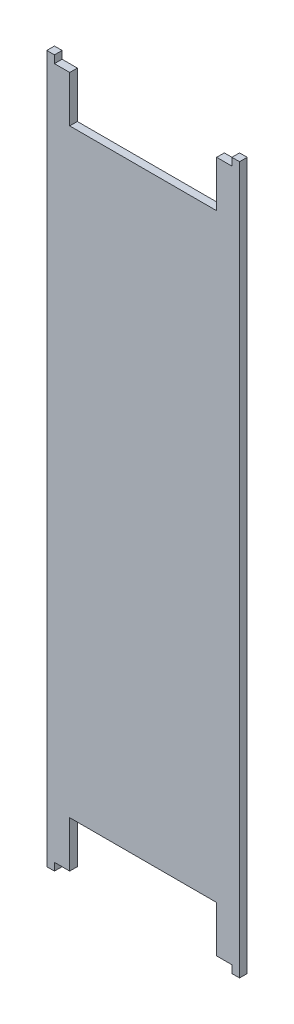
SolidWorks part; units mm, degrees
ref_plane "Front Plane" through (0, 0, 0) normal (0, 0, 1) x (1, 0, 0)
ref_plane "Top Plane" through (0, 0, 0) normal (0, 1, 0) x (1, 0, 0)
ref_plane "Right Plane" through (0, 0, 0) normal (1, 0, 0) x (0, 0, -1)
sketch "Sketch1" plane through (0, 0, 0) normal (0, 0, 1) x (1, 0, 0)
  line L0 (0.9075, 0) -> (-0.9075, 0) construction
  line L1 (-20.825, 76.375) -> (20.825, 76.375)
  line L2 (-20.825, 76.375) -> (-20.825, -76.375)
  line L3 (-20.825, -76.375) -> (20.825, -76.375)
  line L4 (20.825, 76.375) -> (20.825, -76.375)
  line L5 (0, -0.9075) -> (0, 0.9075) construction
  point P6 (20.825, 0)
  point P9 (0, 76.375)
  dimension "D1" = 152.75
  dimension "D2" = 41.65
extrude "Boss-Extrude1" add sketch "Sketch1" along normal blind 1.65
sketch "Sketch2" plane through (0, 0, 1.65) normal (0, 0, 1) x (1, 0, 0)
  line L0 (20.825, -76.375) -> (20.825, 76.375) construction
  line L1 (20.825, 74.725) -> (22.475, 74.725)
  line L2 (20.825, 74.725) -> (20.825, -74.725)
  line L3 (20.825, -74.725) -> (22.475, -74.725)
  line L4 (22.475, 74.725) -> (22.475, -74.725)
  line L5 (20.825, 76.375) -> (-20.825, 76.375) construction
  line L6 (-20.825, -76.375) -> (20.825, -76.375) construction
  line L7 (0, -0.9075) -> (0, 0.9075) construction
  line L8 (-22.475, 74.725) -> (-22.475, -74.725)
  line L9 (-20.825, -74.725) -> (-22.475, -74.725)
  line L10 (-20.825, 74.725) -> (-20.825, -74.725)
  line L11 (-20.825, 74.725) -> (-22.475, 74.725)
  dimension "D1" = 1.65
  dimension "D2" = 1.65
  dimension "D3" = 1.65
extrude "Boss-Extrude2" [suppressed] add sketch "Sketch2" against normal blind 1.65 separate body
sketch "Sketch3" plane through (0, 76.375, 0) normal (0, 1, 0) x (1, 0, 0)
  line L0 (20.825, 0) -> (-20.825, 0) construction
  line L1 (-19.175, 0) -> (19.175, 0)
  line L2 (-19.175, 0) -> (-19.175, -1.65)
  line L3 (-19.175, -1.65) -> (19.175, -1.65)
  line L4 (19.175, 0) -> (19.175, -1.65)
  line L5 (20.825, -1.65) -> (-20.825, -1.65) construction
  line L6 (20.825, -1.65) -> (20.825, 0) construction
  line L7 (-20.825, -1.65) -> (-20.825, 0) construction
  dimension "D1" = 1.65
  dimension "D2" = 1.65
extrude "Cut-Extrude1" cut sketch "Sketch3" against normal blind 1.65
mirror "Mirror1" about plane through (0, 0, 0) normal (0, 1, 0) of "Cut-Extrude1"
sketch "Sketch4" plane through (0, 74.725, 0) normal (0, 1, 0) x (1, 0, 0)
  line L0 (19.175, 0) -> (-19.175, 0) construction
  line L1 (-15.875, 0) -> (15.875, 0)
  line L2 (-15.875, 0) -> (-15.875, -1.65)
  line L3 (-15.875, -1.65) -> (15.875, -1.65)
  line L4 (15.875, 0) -> (15.875, -1.65)
  line L5 (-19.175, -1.65) -> (19.175, -1.65) construction
  line L6 (-19.175, 0) -> (-19.175, -1.65) construction
  line L7 (19.175, -1.65) -> (19.175, 0) construction
  dimension "D1" = 3.3
  dimension "D2" = 3.3
extrude "Cut-Extrude2" cut sketch "Sketch4" against normal blind 10
mirror "Mirror2" about plane through (0, 0, 0) normal (0, 1, 0) of "Cut-Extrude2"
equation "\"Dinoskin scale\"= 2.2"
equation "\"pattern X\"= 3"
equation "\"Pattern Y\"= 9"
equation "\"Base Innerline\"= 0.34"
equation "\"lenght\"= 252"
equation "\"PCB Thickness\"= 1.65"
equation "\"Base Width\"= 4.5"
equation "\"Base Outerline\"= 1"
equation "\"Base Inner to Outer\"= 1"
equation "\"Dinoskin Outerline\"= \"Base Outerline\" * \"Dinoskin scale\""
equation "\"Dinoskin Innerline\"= \"Base Innerline\" * \"Dinoskin scale\""
equation "\"Dinoskin Width\"= \"Base Width\" * \"Dinoskin scale\""
equation "\"Dinoskin Inner to Outer\"= \"Base Inner to Outer\" * \"Dinoskin scale\""
equation "\"Diagonal dist\"= \"Dinoskin Width\" + ( ( \"Dinoskin Innerline\" + \"Dinoskin Outerline\" ) / 2 + \"Dinoskin Inner to Outer\" ) / cos ( 30 )"
equation "\"Dinoskin pattern Y\"= \"Diagonal dist\" * sin ( 30 )"
equation "\"Offset Y\"= 2 * \"Dinoskin pattern Y\""
equation "\"Diagonal dist 2\"= \"Dinoskin Width\" + ( ( \"Dinoskin Innerline\" + \"Dinoskin Outerline\" ) / 2 + 1 ) / cos ( 30 )"
equation "\"Dinoskin pattern X\"= \"Diagonal dist\" * cos ( 30 )"
equation "\"offset x\"= \"Dinoskin pattern X\" * 2"
equation "\"Pattern spacing X\"= \"offset x\" * ( \"pattern X\" - 0.5 ) / 2"
equation "\"Pattern spacing Y\"= \"Offset Y\" *  ( \"Pattern Y\" - 0.5 )  / 2 + 13"
equation "\"offset corner beams\" = 1"
equation "\"D1@Sketch1\"=(\"lenght\" * \"Lenght Ratio\" / 2) - 25 - \"lenght\" / 8 - \"PCB Thickness\" * 3"
equation "\"D2@Sketch1\"= 40 + \"PCB Thickness\""
equation "\"D1@Sketch2\"= \"PCB Thickness\""
equation "\"D2@Sketch2\"=\"PCB Thickness\""
equation "\"D3@Sketch2\"= \"PCB Thickness\""
equation "\"D1@Boss-Extrude2\"=  \"PCB Thickness\""
equation "\"D1@Sketch3\"=\"PCB Thickness\""
equation "\"D2@Sketch3\"=\"PCB Thickness\""
equation "\"D1@Cut-Extrude1\"=\"PCB Thickness\""
equation "\"D8@Sketch3\"=\"Dinoskin Inner to Outer\""
equation "\"D17@Sketch3\"=\"Dinoskin Width\""
equation "\"D6@Sketch3\"=\"Dinoskin Innerline\"/2"
equation "\"D3@Sketch3\"=\"Dinoskin Innerline\"/2"
equation "\"D20@Sketch3\"=\"Dinoskin Outerline\""
equation "\"D19@Sketch3\"=\"Dinoskin Outerline\""
equation "\"D15@Sketch3\"=\"Dinoskin Outerline\"/2"
equation "\"D14@Sketch3\"=\"Dinoskin Outerline\"/2"
equation "\"D10@Sketch3\"=\"Dinoskin Outerline\"/2"
equation "\"D16@Sketch3\"=\"Dinoskin Outerline\"/2"
equation "\"D3@LPattern1\"=\"Dinoskin pattern Y\""
equation "\"D1@Plane1\"=\"PCB Thickness\"/2"
equation "\"D2@LPattern2\"= \"pattern X\""
equation "\"D1@LPattern2\"=\"Pattern Y\""
equation "\"D4@LPattern1\"=\"Dinoskin pattern X\""
equation "\"D3@LPattern2\"= \"Offset Y\""
equation "\"D4@LPattern2\"= \"offset x\""
equation "\"D5@Sketch3\"= \"Pattern spacing X\""
equation "\"D7@Sketch3\"= \"Pattern spacing Y\""
equation "\"D1@Sketch5\"=\"PCB Thickness\""
equation "\"D3@Sketch5\"=\"lenght\" / 64"
equation "\"D5@Sketch5\"= \"offset corner beams\""
equation "\"D6@Sketch5\"=\"offset corner beams\""
equation "\"D1@Sketch6\"= \"lenght\" / 8 + \"PCB Thickness\" * 4"
equation "\"D2@Sketch6\"= \"PCB Thickness\""
equation "\"D3@DinoSkin diagonal pattern\" = \"Dinoskin pattern Y\""
equation "\"D2@Main Dinoskin Array\" = \"pattern X\""
equation "\"D1@Main Dinoskin Array\" = \"Pattern Y\""
equation "\"D4@DinoSkin diagonal pattern\" = \"Dinoskin pattern X\""
equation "\"D3@Main Dinoskin Array\" = \"Offset Y\""
equation "\"D4@Main Dinoskin Array\" = \"offset x\""
equation "\"D1@Sketch8\"=\"PCB Thickness\""
equation "\"D2@Sketch8\"=\"lenght\" / 64"
equation "\"D3@Sketch8\"=\"PCB Thickness\""
equation "\"D4@Sketch8\"= \"lenght\" / 64"
equation "\"D2@Sketch9\"=\"PCB Thickness\""
equation "\"D3@Sketch9\"=\"PCB Thickness\""
equation "\"D4@Sketch6\"=\"PCB Thickness\""
equation "\"D5@Sketch6\"=\"PCB Thickness\""
equation "\"D9@Sketch1\"= \"lenght\" * \"Lenght Ratio\"/2"
equation "\"Lenght Ratio\" = 1.7"
equation "\"D1@Sketch4\"=\"PCB Thickness\"*2"
equation "\"D2@Sketch4\"=\"PCB Thickness\"*2"
